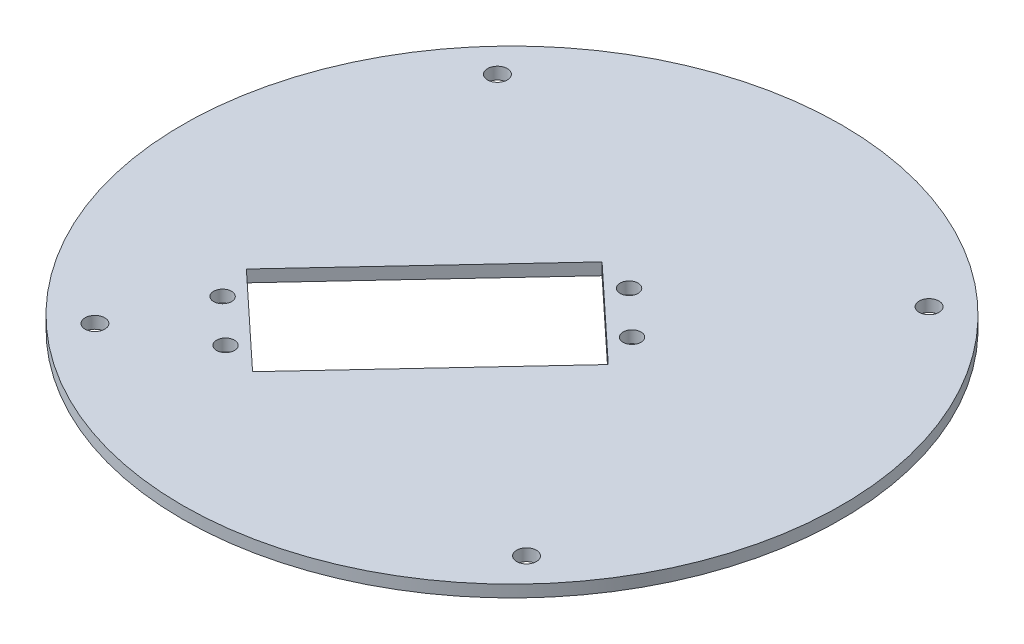
SolidWorks part; units mm, degrees
ref_plane "前视基准面" through (0, 0, 0) normal (0, 0, 1) x (1, 0, 0)
ref_plane "上视基准面" through (0, 0, 0) normal (0, 1, 0) x (1, 0, 0)
ref_plane "右视基准面" through (0, 0, 0) normal (1, 0, 0) x (0, 0, -1)
sketch "草图1" plane through (0, 0, 0) normal (0, 1, 0) x (1, 0, 0)
  circle A0 centre (0, 0) radius 55
  dimension "D1" = 110
extrude "凸台-拉伸1" add sketch "草图1" along normal blind 2
sketch "草图2" plane through (0, 2, 0) normal (0, 1, 0) x (1, 0, 0)
  line L1 (36.0169, -33.5909) -> (33.5909, 36.0169)
  line L2 (33.5909, 36.0169) -> (-36.0169, 33.5909)
  line L3 (-36.0169, 33.5909) -> (-33.5909, -36.0169)
  line L4 (-33.5909, -36.0169) -> (36.0169, -33.5909)
  circle A0 centre (0, 0) radius 49.25 construction
  circle A1 centre (-36.0169, 33.5909) radius 1.65
  circle A2 centre (33.5909, 36.0169) radius 1.65
  circle A3 centre (36.0169, -33.5909) radius 1.65
  circle A4 centre (-33.5909, -36.0169) radius 1.65
extrude "切除-拉伸1" cut sketch "草图2" against normal blind 2 contours A3
extrude "切除-拉伸3" cut sketch "草图2<4>" against normal blind 2 contours A4 | A1 | A2
sketch "草图2<4>" plane through (0, 2, 0) normal (0, 1, 0) x (1, 0, 0) same geometry as "草图2"
sketch "草图3" plane through (0, 2, 0) normal (0, 1, 0) x (1, 0, 0)
  line L0 (33.5909, 36.0169) -> (-33.5909, -36.0169) construction
  line L1 (-28.8222, -15.509) -> (-0.1762, 15.2059)
  line L2 (-0.1762, 15.2059) -> (15.1813, 0.8829)
  line L3 (15.1813, 0.8829) -> (-13.4648, -29.832)
  line L4 (-13.4648, -29.832) -> (-28.8222, -15.509)
  circle A1 centre (-26.8462, -21.4542) radius 1.5
  circle A2 centre (-19.5331, -28.2747) radius 1.5
  circle A3 centre (5.8921, 13.6485) radius 1.5
  circle A4 centre (13.2052, 6.8281) radius 1.5
  point P6 (-21.1435, -22.6705)
  dimension "D5" = 48
  dimension "D13" = 3
  dimension "D14" = 3
  dimension "D15" = 3
  dimension "D16" = 3
  dimension "D1" = 10.5
  dimension "D2" = 21
  dimension "D3" = 31
  dimension "D4" = 42
  dimension "D6" = 3
  dimension "D7" = 3
  dimension "D8" = 3
  dimension "D9" = 3
  dimension "D10" = 5
  dimension "D11" = 5
  dimension "D12" = 5
extrude "切除-拉伸4" cut sketch "草图3" against normal blind 10
